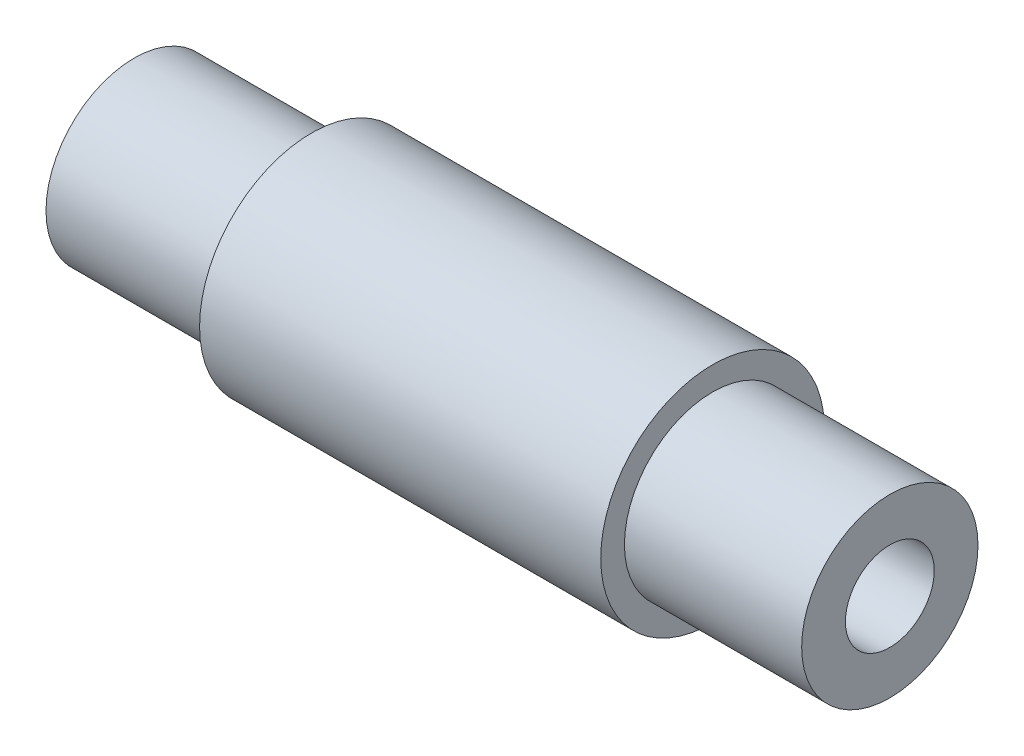
SolidWorks part; units mm, degrees
ref_plane "Front Plane" through (0, 0, 0) normal (0, 0, 1) x (1, 0, 0)
ref_plane "Top Plane" through (0, 0, 0) normal (0, 1, 0) x (1, 0, 0)
ref_plane "Right Plane" through (0, 0, 0) normal (1, 0, 0) x (0, 0, -1)
sketch "Filter_F2_T6 Sketch" plane through (0, 0, 0) normal (0, 0, 1) x (1, 0, 0)
  line L0 (-1000, 0) -> (1000, 0) construction
  line L1 (-40.5, 0) -> (-40.5, 9.45)
  line L2 (-40.5, 9.45) -> (-21.5, 9.45)
  line L3 (-21.5, 9.45) -> (-21.5, 11.988)
  line L4 (-21.5, 11.988) -> (21.5, 11.988)
  line L5 (21.5, 11.988) -> (21.5, 9.45)
  line L6 (21.5, 9.45) -> (40.5, 9.45)
  line L7 (40.5, 9.45) -> (40.5, 0)
  line L8 (40.5, 0) -> (-40.5, 0)
revolve "Filter_F2_T6" add sketch "Filter_F2_T6 Sketch" angle 360 about L0
ref_axis "Engine Axis" through (44.55, 0, 0) along (-1, 0, 0)
sketch "Socket 1 Sketch" plane through (0, 0, 0) normal (0, 0, 1) x (1, 0, 0)
  line L0 (-1000, 0) -> (1000, 0) construction
  line L1 (-41.5, 0) -> (-41.5, 4.7625)
  line L2 (-41.5, 4.7625) -> (-23.7, 4.7625)
  line L3 (-23.7, 4.7625) -> (-23.7, 0)
  line L4 (-23.7, 0) -> (-41.5, 0)
revolve "Socket 1" cut sketch "Socket 1 Sketch" angle 360 about L0
sketch "Socket 2 Sketch" plane through (0, 0, 0) normal (0, 0, 1) x (1, 0, 0)
  line L0 (-1000, 0) -> (1000, 0) construction
  line L1 (23.7, 0) -> (23.7, 4.7625)
  line L2 (23.7, 4.7625) -> (41.5, 4.7625)
  line L3 (41.5, 4.7625) -> (41.5, 0)
  line L4 (41.5, 0) -> (23.7, 0)
revolve "Socket 2" cut sketch "Socket 2 Sketch" angle 360 about L0
